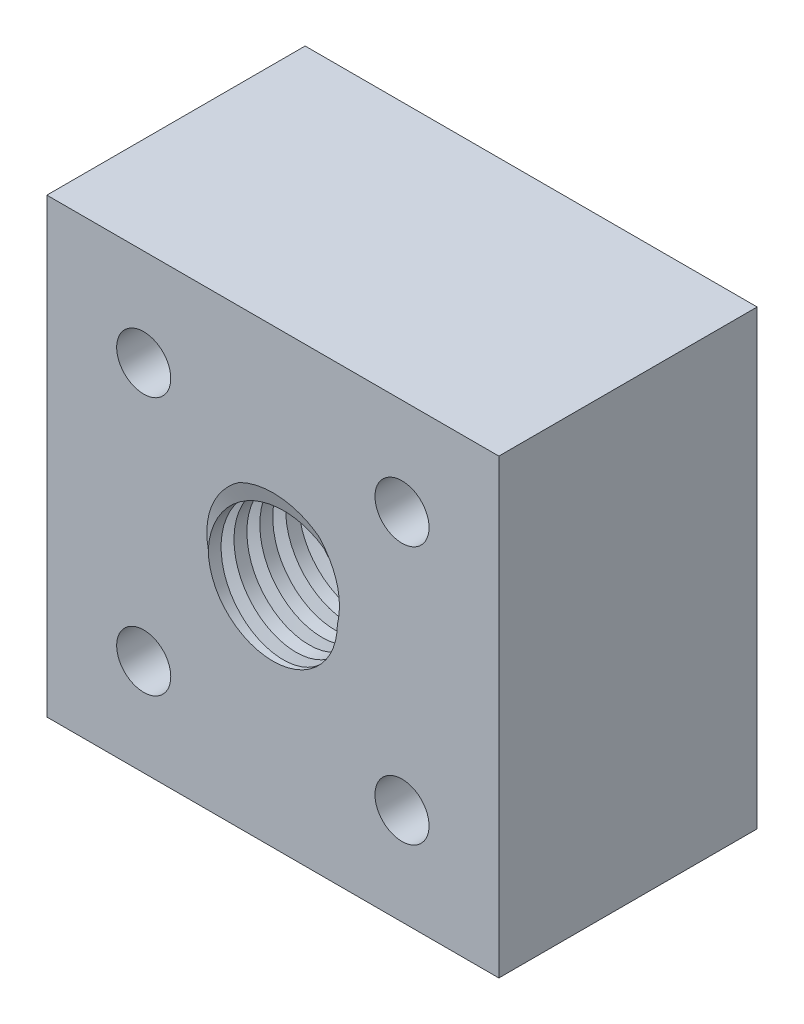
SolidWorks part; units mm, degrees
material "3003-O"
ref_plane "Front Plane" through (0, 0, 0) normal (0, 0, 1) x (1, 0, 0)
ref_plane "Top Plane" through (0, 0, 0) normal (0, 1, 0) x (1, 0, 0)
ref_plane "Right Plane" through (0, 0, 0) normal (1, 0, 0) x (0, 0, -1)
sketch "Sketch1" plane through (0, 0, 0) normal (0, 0, 1) x (1, 0, 0)
  line L1 (-17.5, -17.5) -> (17.5, -17.5)
  line L2 (-17.5, -17.5) -> (-17.5, 17.5)
  line L3 (-17.5, 17.5) -> (17.5, 17.5)
  line L4 (17.5, -17.5) -> (17.5, 17.5)
  line L5 (-17.5, -17.5) -> (17.5, 17.5) construction
  line L6 (-17.5, 17.5) -> (17.5, -17.5) construction
  circle A0 centre (-10, 10) radius 2.0942
  circle A1 centre (10, 10) radius 2.0942
  circle A2 centre (10, -10) radius 2.0942
  circle A3 centre (-10, -10) radius 2.0942
  circle A4 centre (0, 0) radius 5
  point P0 (0, 0)
  dimension "D1" = 10
  dimension "D2" = 10
  dimension "D4" = 10
  dimension "D3" = 35
extrude "Boss-Extrude1" add sketch "Sketch1" along normal blind 20
sketch "Sketch2" plane through (0, 0, 0) normal (0, 1, 0) x (1, 0, 0)
  line L1 (-400.6751, -5) -> (-399.6751, -5)
  line L2 (-400.6751, -5) -> (-400.3681, -3.75)
  line L4 (-399.6751, -5) -> (-400.0383, -3.75)
  arc A0 (-400.3681, -3.75) -> (-400.0383, -3.75) centre (-400.2032, -4.0006) cw
  dimension "D1" = 1.25
  dimension "D2" = 1.25
  dimension "D3" = 1
  dimension "D4" = 30
sketch "Sketch4" plane through (0, 0, 0) normal (1, 0, 0) x (0, 0, -1)
  line L0 (-20.5, 5) -> (-19.5, 5)
  line L1 (-20.5, 5) -> (-20.193, 6.25)
  line L2 (-19.5, 5) -> (-19.8632, 6.25)
  arc A0 (-20.193, 6.25) -> (-19.8632, 6.25) centre (-20.0281, 5.9994) cw
  dimension "D1" = 1.25
  dimension "D2" = 1.25
  dimension "D3" = 1
  dimension "D4" = 30
  dimension "D5" = 76.2
sketch "Sketch5" plane through (0, 0, 20) normal (0, 0, 1) x (1, 0, 0)
  circle A0 centre (0, 0) radius 5
curve "Helix/Spiral1" pitch 2 height 21.5 turns 10.75
sweep "Cut-Sweep1" cut profiles "Sketch4" path "Helix/Spiral1"
